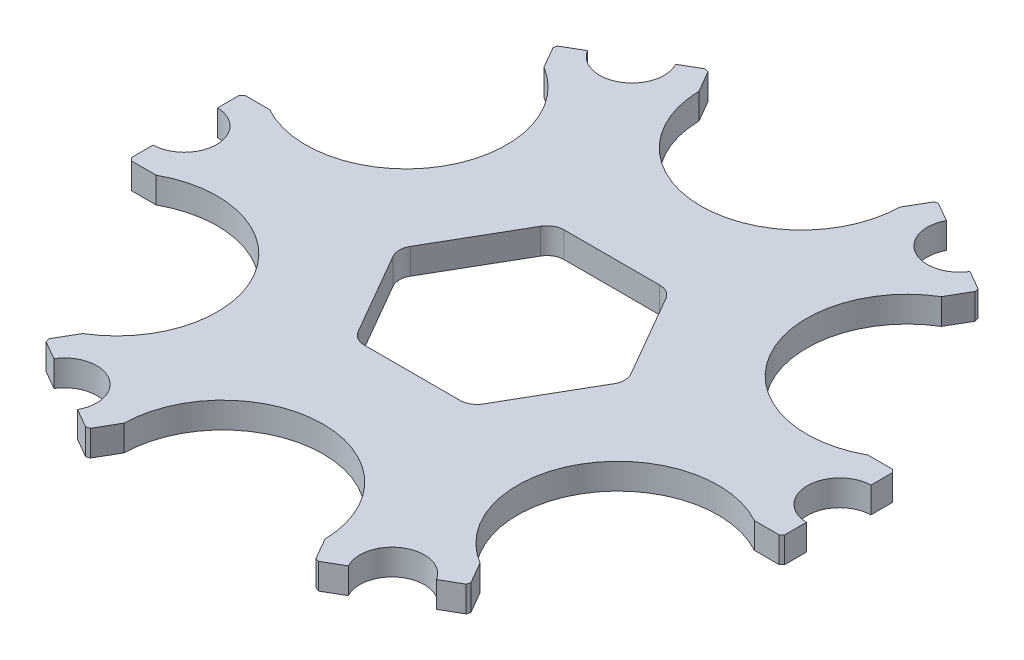
SolidWorks part; units mm, degrees
material "6061-T6 (SS)"
ref_plane "Front Plane" through (0, 0, 0) normal (0, 0, 1) x (1, 0, 0)
ref_plane "Top Plane" through (0, 0, 0) normal (0, 1, 0) x (1, 0, 0)
ref_plane "Right Plane" through (0, 0, 0) normal (1, 0, 0) x (0, 0, -1)
sketch "Sketch1" plane through (0, 0, 0) normal (0, 1, 0) x (1, 0, 0)
  line L0 (0, 0) -> (-62.5623, 0) construction
  line L1 (10.6319, 18.415) -> (-10.6319, 18.415)
  line L2 (-10.6319, 18.415) -> (-21.2638, 0)
  line L3 (-21.2638, 0) -> (-10.6319, -18.415)
  line L4 (-10.6319, -18.415) -> (10.6319, -18.415)
  line L5 (10.6319, -18.415) -> (21.2638, 0)
  line L6 (21.2638, 0) -> (10.6319, 18.415)
  line L7 (-60.2361, 10.4648) -> (-60.2361, 5.9505)
  line L8 (-60.4139, 0) -> (-60.4139, -29.149) construction
  line L9 (-60.2361, -5.9505) -> (-60.2361, -10.4648)
  line L10 (-35.2713, 49.1908) -> (-39.1808, 46.9336)
  line L11 (-21.0553, 57.3984) -> (-24.9648, 55.1412)
  line L12 (24.9648, 55.1412) -> (21.0553, 57.3984)
  line L13 (39.1808, 46.9336) -> (35.2713, 49.1908)
  line L14 (60.2361, 5.9505) -> (60.2361, 10.4648)
  line L15 (60.2361, -10.4648) -> (60.2361, -5.9505)
  line L16 (35.2713, -49.1908) -> (39.1808, -46.9336)
  line L17 (21.0553, -57.3984) -> (24.9648, -55.1412)
  line L18 (-24.9648, -55.1412) -> (-21.0553, -57.3984)
  line L19 (-39.1808, -46.9336) -> (-35.2713, -49.1908)
  line L20 (-60.2361, 10.4648) -> (-55.1561, 10.4648)
  line L21 (-39.1808, 46.9336) -> (-36.6408, 42.5342)
  line L22 (-21.0553, 57.3984) -> (-18.5153, 52.999)
  line L23 (21.0553, 57.3984) -> (18.5153, 52.999)
  line L24 (39.1808, 46.9336) -> (36.6408, 42.5342)
  line L25 (60.2361, 10.4648) -> (55.1561, 10.4648)
  line L26 (60.2361, -10.4648) -> (55.1561, -10.4648)
  line L27 (39.1808, -46.9336) -> (36.6408, -42.5342)
  line L28 (21.0553, -57.3984) -> (18.5153, -52.999)
  line L29 (-21.0553, -57.3984) -> (-18.5153, -52.999)
  line L30 (-39.1808, -46.9336) -> (-36.6408, -42.5342)
  line L31 (-60.2361, -10.4648) -> (-55.1561, -10.4648)
  line L32 (21.0553, 57.3984) -> (18.5153, 52.999)
  line L33 (-21.0553, 57.3984) -> (-18.5153, 52.999)
  line L34 (60.2361, 10.4648) -> (55.1561, 10.4648)
  line L35 (39.1808, 46.9336) -> (36.6408, 42.5342)
  line L36 (39.1808, -46.9336) -> (36.6408, -42.5342)
  line L37 (60.2361, -10.4648) -> (55.1561, -10.4648)
  line L38 (-21.0553, -57.3984) -> (-18.5153, -52.999)
  line L39 (21.0553, -57.3984) -> (18.5153, -52.999)
  line L40 (-60.2361, -10.4648) -> (-55.1561, -10.4648)
  line L41 (-39.1808, -46.9336) -> (-36.6408, -42.5342)
  circle A0 centre (0, 0) radius 18.415 construction
  arc A2 (-60.4139, 5.9531) -> (-60.4139, -5.9531) centre (-60.4139, 0) ccw construction
  arc A8 (-60.2361, 5.9505) -> (-60.2361, -5.9505) centre (-60.4139, 0) cw
  arc A9 (-60.2361, -5.9505) -> (-60.2361, 5.9505) centre (-60.4139, 0) ccw construction
  arc A10 (-24.9648, 55.1412) -> (-35.2713, 49.1908) centre (-30.207, 52.32) cw
  arc A11 (35.2713, 49.1908) -> (24.9648, 55.1412) centre (30.2069, 52.32) cw
  arc A12 (60.2361, -5.9505) -> (60.2361, 5.9505) centre (60.4139, 0) cw
  arc A13 (24.9648, -55.1412) -> (35.2713, -49.1908) centre (30.207, -52.32) cw
  arc A14 (-35.2713, -49.1908) -> (-24.9648, -55.1412) centre (-30.2069, -52.32) cw
  arc A27 (-55.1561, 10.4648) -> (-36.6408, 42.5342) centre (-46.1938, 26.67) ccw
  arc A28 (-18.5153, 52.999) -> (18.5153, 52.999) centre (0, 53.34) ccw
  arc A29 (36.6408, 42.5342) -> (55.1561, 10.4648) centre (46.1938, 26.67) ccw
  arc A30 (55.1561, -10.4648) -> (36.6408, -42.5342) centre (46.1938, -26.67) ccw
  arc A31 (18.5153, -52.999) -> (-18.5153, -52.999) centre (0, -53.34) ccw
  arc A32 (-36.6408, -42.5342) -> (-55.1561, -10.4648) centre (-46.1938, -26.67) ccw
  point P27 (0, 0)
  point P58 (0, 0)
  point P74 (0, 0)
  point P87 (0, 0)
  point P98 (0, 0)
  dimension "D1" = 11.9062
  dimension "D10" = 6
  dimension "D2" = 60.4139
  dimension "D3" = 36.83
  dimension "D6" = 0.3556
  dimension "D7" = 20.9296
  dimension "D9" = 5.08
  dimension "D11" = 53.34
  dimension "D8" = 6
  dimension "D12" = 6
extrude "Boss-Extrude1" add sketch "Sketch1" along normal blind 4.7625 contours L18 L17 A13 L16 L15 A12 L14 L13 A11 L12 L11 A10 L10 L7 A8 L9 L19 A14 L3 L2 L1 L6 L5 L4 region at (-57.6961, 0, -8.8007)
chamfer "Chamfer1" distance 0.508 angle 45 12 edges at (-60.2361, 2.3813, 10.4648) (-39.1808, 2.3813, 46.9336) (-21.0553, 2.3813, 57.3984) (21.0553, 2.3813, 57.3984) (39.1808, 2.3813, 46.9336) (60.2361, 2.3813, 10.4648) (60.2361, 2.3813, -10.4648) (39.1808, 2.3813, -46.9336) (21.0553, 2.3813, -57.3984) (-21.0553, 2.3813, -57.3984) (-39.1808, 2.3813, -46.9336) (-60.2361, 2.3813, -10.4648)
sketch "Sketch3" plane through (0, 0, 0) normal (0, 0, 1) x (1, 0, 0)
  line L0 (0, 32.7405) -> (0, -26.7673) construction
ref_axis "Axis1" through (0, 32.7405, 0) along (0, -1, 0)
fillet "Fillet1" radius 3.175 6 edges at (-21.2638, 2.3813, 0) (-10.6319, 2.3813, 18.415) (10.6319, 2.3813, 18.415) (21.2638, 2.3813, 0) (10.6319, 2.3813, -18.415) (-10.6319, 2.3813, -18.415)
move or copy body "Body-Move/Copy1" [suppressed] bodies to move or copy 101 parameters "D1"=0, "D2"=0, "D3"=0
